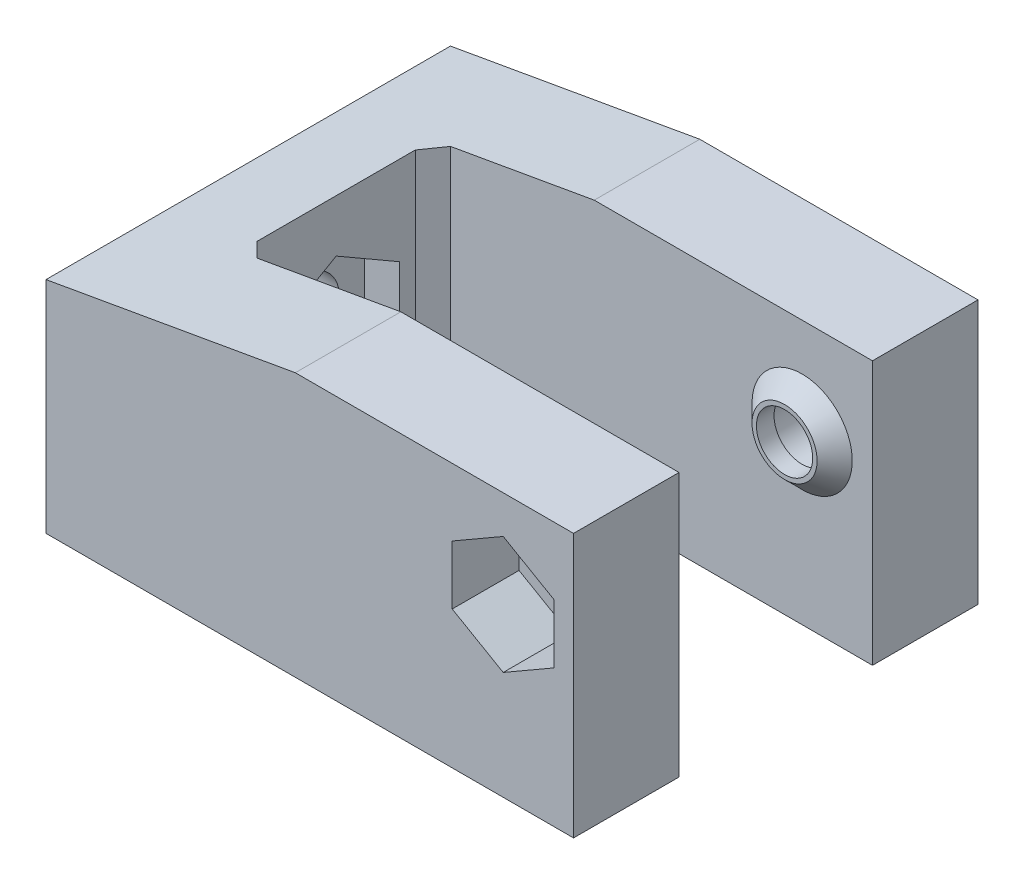
SolidWorks part; units mm, degrees
ref_plane "Front Plane" through (0, 0, 0) normal (0, 0, 1) x (1, 0, 0)
ref_plane "Top Plane" through (0, 0, 0) normal (0, 1, 0) x (1, 0, 0)
ref_plane "Right Plane" through (0, 0, 0) normal (1, 0, 0) x (0, 0, -1)
sketch "Sketch1" plane through (0, 0, 0) normal (1, 0, 0) x (0, 0, -1)
  line L1 (0, 0) -> (23, 0)
  line L2 (0, 0) -> (0, 15)
  line L3 (0, 15) -> (23, 15)
  line L4 (23, 0) -> (23, 15)
  dimension "D1" = 23
  dimension "D2" = 15
extrude "Boss-Extrude1" add sketch "Sketch1" along normal blind 30
sketch "Sketch2" plane through (30, 0, 0) normal (1, 0, 0) x (0, 0, -1)
  line L0 (11.5, 15) -> (11.5, 0) construction
  line L1 (6, 15) -> (17, 15)
  line L2 (6, 15) -> (6, 0)
  line L3 (6, 0) -> (17, 0)
  line L4 (17, 15) -> (17, 0)
  line L5 (0, 0) -> (23, 0) construction
  line L8 (23, 15) -> (0, 15) construction
  line L9 (11.5, 15) -> (11.5, 0) construction
  dimension "D1" = 11
extrude "Cut-Extrude1" cut sketch "Sketch2" against normal offset from surface (25 mm away) 5 up to face at (0, 7.5, -11.5)
sketch "Sketch3" plane through (0, 0, -23) normal (0, 0, -1) x (-1, 0, 0)
  line L1 (-30, 0) -> (-30, 15) construction
  line L2 (-30, 0) -> (0, 0) construction
  circle A0 centre (-26, 9.5) radius 1.7
  dimension "D3" = 3.4
  dimension "D1" = 9.5
  dimension "D2" = 4
extrude "Cut-Extrude2" cut sketch "Sketch3" against normal through all both and the other way through all
chamfer "Chamfer1" distance 2.5 angle 80 1 edges at (0, 15, -11.5) first distance on face at (0, 7.5, -11.5)
sketch "Sketch4" plane through (0, 0, 0) normal (-1, 0, 0) x (0, 0, 1)
  line L0 (-11.5, 12.5) -> (-11.5, 0) construction
  line L1 (0, 12.5) -> (-23, 12.5) construction
  line L2 (0, 0) -> (-23, 0) construction
  line L3 (-23, 6.25) -> (0, 6.25) construction
  line L4 (-23, 0) -> (-23, 12.5) construction
  line L5 (0, 12.5) -> (0, 0) construction
  circle A0 centre (-11.5, 6.25) radius 2.2
  dimension "D1" = 4.4
extrude "Cut-Extrude3" cut sketch "Sketch4" against normal blind 10
sketch "Sketch5" plane through (5, 0, 0) normal (1, 0, 0) x (0, 0, -1)
  line L1 (7.9, 8.3285) -> (7.9, 4.1715)
  line L2 (7.9, 4.1715) -> (11.5, 2.0931)
  line L3 (11.5, 2.0931) -> (15.1, 4.1715)
  line L4 (15.1, 4.1715) -> (15.1, 8.3285)
  line L5 (15.1, 8.3285) -> (11.5, 10.4069)
  line L6 (11.5, 10.4069) -> (7.9, 8.3285)
  circle A0 centre (11.5, 6.25) radius 3.6 construction
  dimension "D1" = 7.2
extrude "Cut-Extrude4" cut sketch "Sketch5" against normal blind 2
sketch "Sketch6" plane through (0, 0, -23) normal (0, 0, -1) x (-1, 0, 0)
  circle A0 centre (-26, 9.5) radius 3.25
  dimension "D1" = 6.5
extrude "Cut-Extrude5" cut sketch "Sketch6" against normal blind 2.5
sketch "Sketch7" plane through (0, 0, 0) normal (0, 0, 1) x (1, 0, 0)
  line L1 (23.1, 11.1743) -> (23.1, 7.8257)
  line L2 (23.1, 7.8257) -> (26, 6.1514)
  line L3 (26, 6.1514) -> (28.9, 7.8257)
  line L4 (28.9, 7.8257) -> (28.9, 11.1743)
  line L5 (28.9, 11.1743) -> (26, 12.8486)
  line L6 (26, 12.8486) -> (23.1, 11.1743)
  circle A0 centre (26, 9.5) radius 2.9 construction
  dimension "D1" = 5.8
extrude "Cut-Extrude6" cut sketch "Sketch7" against normal blind 3.8
sketch "Sketch8" plane through (0, 0, -17) normal (0, 0, 1) x (1, 0, 0)
  circle A0 centre (26, 9.5) radius 1.85
  circle A1 centre (26, 9.5) radius 1.6009
  dimension "D1" = 3.7
  dimension "D2" = 3.2017
sketch "Sketch9" plane through (0, 0, -6) normal (0, 0, -1) x (-1, 0, 0)
  circle A0 centre (-26, 9.5) radius 1.6
  circle A1 centre (-26, 9.5) radius 1.85
  dimension "D1" = 3.7
  dimension "D2" = 3.2
chamfer "Chamfer3" distance 1 angle 45 2 edges at (5, 6.6908, -6) (5, 6.6908, -17)
extrude "Boss-Extrude2" add sketch "Sketch9" along normal blind 1
extrude "Boss-Extrude3" add sketch "Sketch8" along normal blind 1
chamfer "Chamfer4" distance 1 angle 45 2 edges at (26, 7.65, -6) (24.15, 9.5, -17)
